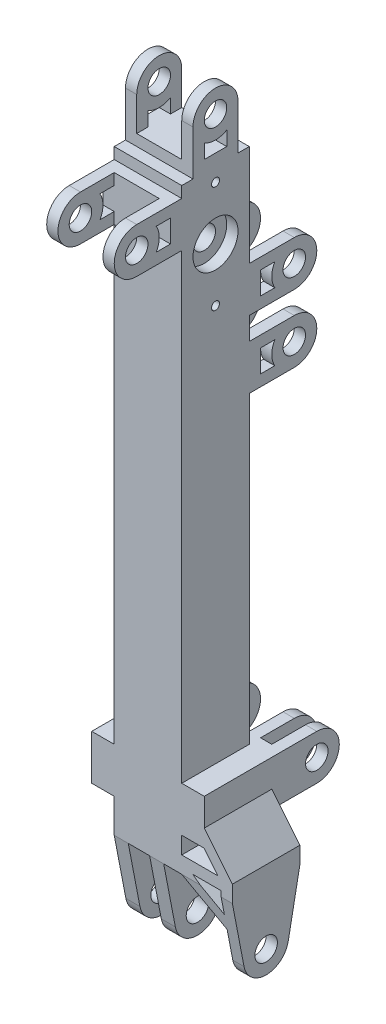
SolidWorks part; units mm, degrees
ref_plane "Front Plane" through (0, 0, 0) normal (0, 0, 1) x (1, 0, 0)
ref_plane "Top Plane" through (0, 0, 0) normal (0, 1, 0) x (1, 0, 0)
ref_plane "Right Plane" through (0, 0, 0) normal (1, 0, 0) x (0, 0, -1)
sketch "Sketch1" plane through (0, 0, 0) normal (0, 1, 0) x (1, 0, 0)
  line L1 (-9.525, -9.525) -> (9.525, -9.525)
  line L2 (-9.525, -9.525) -> (-9.525, 9.525)
  line L3 (-9.525, 9.525) -> (9.525, 9.525)
  line L4 (9.525, -9.525) -> (9.525, 9.525)
  line L5 (-9.525, -9.525) -> (9.525, 9.525) construction
  line L6 (-9.525, 9.525) -> (9.525, -9.525) construction
  point P0 (0, 0)
  dimension "D1" = 19.05
extrude "Boss-Extrude1" add sketch "Sketch1" along normal blind 190.5
sketch "Sketch2" plane through (0, 0, 0) normal (0, 1, 0) x (1, 0, 0)
  line L1 (-6.35, -6.35) -> (6.35, -6.35)
  line L2 (-6.35, -6.35) -> (-6.35, 6.35)
  line L3 (-6.35, 6.35) -> (6.35, 6.35)
  line L4 (6.35, -6.35) -> (6.35, 6.35)
  line L5 (-6.35, -6.35) -> (6.35, 6.35) construction
  line L6 (-6.35, 6.35) -> (6.35, -6.35) construction
  point P0 (0, 0)
  dimension "D1" = 12.7
extrude "Cut-Extrude1" cut sketch "Sketch2" along normal blind 120.65 from offset 25.4 contours L3 L4 L1 L2
sketch "Sketch4" plane through (0, 0, 0) normal (1, 0, 0) x (0, 0, -1)
  line L0 (-9.525, 190.5) -> (9.525, 190.5) construction
  circle A0 centre (0, 171.45) radius 6.35
  dimension "D1" = 12.7
  dimension "D2" = 19.05
extrude "Cut-Extrude2" cut sketch "Sketch4" against normal blind 3.175 from surface contours A0 starting at face at (9.525, 95.25, 0)
extrude "Cut-Extrude3" cut sketch "Sketch4<3>" along normal blind 3.175 from surface starting at face at (-9.525, 95.25, 0)
sketch "Sketch4<3>" plane through (0, 0, 0) normal (1, 0, 0) x (0, 0, -1) same geometry as "Sketch4"
sketch "Sketch5" plane through (0, 0, 0) normal (1, 0, 0) x (0, 0, -1)
  circle A0 centre (0, 171.45) radius 3.175
  dimension "D1" = 6.35
extrude "Cut-Extrude4" cut sketch "Sketch5" against normal through all both and the other way through all contours A0
hole_wizard "#4-40 Tapped Hole1" positions "Sketch6" profile "Sketch7" tap size "#4-40" standard "ANSI Inch" end condition through all
sketch "Sketch6" plane through (9.525, 0, 0) normal (1, 0, 0) x (0, 0, -1)
  line L0 (0, 186.5312) -> (0, 156.3688) construction
  circle A0 centre (0, 171.45) radius 3.175 construction
  point P0 (0, 186.5312)
  point P2 (0, 156.3688)
  point P9 (0, 171.45)
  dimension "D1" = 30.1625
sketch "Sketch7" plane through (9.525, 186.5312, 0) normal (0, 1, 0) x (0, 0, -1)
  line L0 (0, 0) -> (0, 19.05)
  line L1 (0, 19.05) -> (1.1303, 19.05)
  line L2 (1.1303, 19.05) -> (1.1303, 0)
  line L5 (1.1303, 0) -> (0, 0)
  line L11 (0, -6.35) -> (0, 107.95) construction
  dimension "Thru Tap Drill Dia." = 2.2606
  dimension "Thru Tap Drill Depth" = 19.05
cosmetic thread "Hole Thread1" parameters "D2"=2.8448
cosmetic thread "Hole Thread2" parameters "D2"=2.8448
sketch "Sketch8" plane through (0, 0, 0) normal (1, 0, 0) x (0, 0, -1)
  line L0 (-9.525, 25.4) -> (9.525, 25.4) construction
  line L1 (-9.525, 190.5) -> (-9.525, 0) construction
  line L2 (9.525, 190.5) -> (9.525, 0) construction
  line L4 (9.525, 22.225) -> (6.2354, 5.1488)
  line L5 (-6.2354, 5.1488) -> (-9.525, 22.225)
  line L7 (-9.525, 0) -> (9.525, 0) construction
  line L8 (-9.525, 22.225) -> (-9.525, 0)
  line L9 (-9.525, 0) -> (0, 0)
  line L10 (0, 0) -> (9.525, 0)
  line L11 (9.525, 0) -> (9.525, 22.225)
  arc A0 (6.2354, 5.1488) -> (-6.2354, 5.1488) centre (0, 6.35) cw
  circle A1 centre (0, 6.35) radius 3.175
  dimension "D3" = 6.35
  dimension "D4" = 6.35
  dimension "D1" = 3.175
  dimension "D2" = 19.05
extrude "Cut-Extrude5" cut sketch "Sketch8" against normal through all both and the other way through all contours L9 A0 L5 L8 | L4 A0 L10 L11 | A1 region at (0, 6.7606, -7.7085) region at (0, 6.7606, 7.7085) region at (0, 6.35, 0)
sketch "Sketch9" plane through (0, 0, 0) normal (0, 0, 1) x (1, 0, 0)
  line L0 (-9.525, 22.225) -> (9.525, 22.225) construction
  line L12 (0, 0) -> (0, 42.162) construction
  line L13 (-5.5562, 22.225) -> (-5.5563, 0)
  line L14 (0.4673, 0) -> (-5.5563, 0)
  line L15 (0.4673, 22.225) -> (0.4673, 0)
  line L16 (0.4673, 22.225) -> (-5.5562, 22.225)
  line L17 (4.4361, 22.225) -> (4.4361, 0)
  line L18 (9.525, 0) -> (4.4361, 0)
  line L19 (9.525, 22.225) -> (9.525, 0)
  line L20 (9.525, 22.225) -> (4.4361, 22.225)
  line L21 (9.525, 5.1488) -> (9.525, 22.225) construction
  line L22 (-9.525, 0) -> (9.525, 0) construction
  line L24 (-9.525, 5.1488) -> (-9.525, 22.225) construction
  dimension "D2" = 3.9688
  dimension "D3" = 6.0236
  dimension "D4" = 3.9687
extrude "Cut-Extrude6" cut sketch "Sketch9" against normal through all both and the other way through all
hole_wizard "#4-40 Tapped Hole2" positions "Sketch10" profile "Sketch11" tap size "#4-40" standard "ANSI Inch" end condition up to next
sketch "Sketch10" plane through (-9.525, 0, 0) normal (-1, 0, 0) x (0, 0, 1)
  point P0 (0, 20.6375)
  point P2 (0, 14.2875)
  dimension "D1" = 1.5875
  dimension "D2" = 6.35
sketch "Sketch11" plane through (-9.525, 20.6375, 0) normal (0, 1, 0) x (0, 0, 1)
  line L0 (0, 0) -> (0, 3.9688)
  line L1 (0, 3.9688) -> (1.1303, 3.9688)
  line L2 (1.1303, 3.9688) -> (1.1303, 0)
  line L5 (1.1303, 0) -> (0, 0)
  line L11 (0, -6.35) -> (0, 107.95) construction
  dimension "Thru Tap Drill Dia." = 2.2606
  dimension "Thru Tap Drill Depth" = 3.9688
cosmetic thread "Hole Thread3" parameters "D2"=2.8448
cosmetic thread "Hole Thread4" parameters "D2"=2.8448
sketch "Sketch12" plane through (0, 0, 0) normal (1, 0, 0) x (0, 0, -1)
  line L0 (-9.525, 187.325) -> (-9.525, 174.625)
  line L1 (-9.525, 190.5) -> (-9.525, 22.225) construction
  line L2 (-9.525, 174.625) -> (-22.225, 174.625)
  line L3 (-9.525, 187.325) -> (-22.225, 187.325)
  line L4 (-12.7, 184.15) -> (-12.7, 177.8)
  line L5 (-12.7, 177.8) -> (-16.7257, 177.8)
  line L6 (-12.7, 184.15) -> (-16.7257, 184.15)
  line L7 (-14.7129, 184.15) -> (-14.7129, 187.325) construction
  line L8 (-14.7129, 177.8) -> (-14.7129, 174.625) construction
  line L9 (-12.7, 180.975) -> (-9.525, 180.975) construction
  line L10 (-9.525, 190.5) -> (9.525, 190.5) construction
  arc A0 (-22.225, 187.325) -> (-22.225, 174.625) centre (-22.225, 180.975) ccw
  circle A1 centre (-22.225, 180.975) radius 3.175
  arc A2 (-16.7257, 184.15) -> (-16.7257, 177.8) centre (-22.225, 180.975) cw
  dimension "D2" = 6.35
  dimension "D3" = 12.7
  dimension "D1" = 12.7
  dimension "D4" = 3.175
  dimension "D5" = 9.525
extrude "Boss-Extrude2" add sketch "Sketch12" along normal up to surface and the other way up to surface up to face at (9.525, 106.3625, 0) other way up to face at (-9.525, 71.7665, 0)
sketch "Sketch13" plane through (0, 187.325, 0) normal (0, 1, 0) x (1, 0, 0)
  line L0 (-9.525, -28.575) -> (9.525, -28.575) construction
  line L1 (-6.35, -12.7) -> (6.35, -12.7)
  line L2 (-6.35, -12.7) -> (-6.35, -28.575)
  line L3 (-6.35, -28.575) -> (6.35, -28.575)
  line L4 (6.35, -12.7) -> (6.35, -28.575)
  line L5 (0, -12.7) -> (0, 0) construction
  line L6 (9.525, -22.225) -> (9.525, -9.525) construction
  line L7 (9.525, -9.525) -> (-9.525, -9.525) construction
  dimension "D1" = 3.175
  dimension "D2" = 3.175
extrude "Cut-Extrude7" cut sketch "Sketch13" against normal up to next contours L2 L3 L4 L1
sketch "Sketch15" plane through (0, 0, 0) normal (1, 0, 0) x (0, 0, -1)
  line L11 (-6.35, 190.5) -> (6.35, 190.5)
  line L12 (-9.525, 190.5) -> (9.525, 190.5) construction
  line L13 (6.35, 190.5) -> (6.35, 203.2)
  line L14 (-6.35, 203.2) -> (-6.35, 190.5)
  line L15 (-3.175, 193.675) -> (3.175, 193.675)
  line L16 (3.175, 193.675) -> (3.175, 197.7007)
  line L17 (-3.175, 193.675) -> (-3.175, 197.7007)
  line L18 (0, 190.5) -> (0, 193.675) construction
  line L19 (3.175, 195.6879) -> (6.35, 195.6879) construction
  line L20 (-3.175, 195.6879) -> (-6.35, 195.6879) construction
  arc A3 (6.35, 203.2) -> (-6.35, 203.2) centre (0, 203.2) ccw
  circle A4 centre (0, 203.2) radius 3.175
  arc A5 (-3.175, 197.7007) -> (3.175, 197.7007) centre (0, 203.2) ccw
  dimension "D8" = 6.35
  dimension "D5" = 12.7
  dimension "D6" = 12.7
  dimension "D7" = 3.175
extrude "Boss-Extrude3" add sketch "Sketch15" along normal up to surface and the other way up to surface up to face at (9.525, 143.6687, 8.7313) other way up to face at (-9.525, 115.4499, 6.985)
sketch "Sketch16" plane through (0, 0, -6.35) normal (0, 0, -1) x (-1, 0, 0)
  line L0 (9.525, 209.55) -> (-9.525, 209.55) construction
  line L1 (-6.35, 209.55) -> (6.35, 209.55)
  line L2 (-6.35, 209.55) -> (-6.35, 193.675)
  line L3 (-6.35, 193.675) -> (6.35, 193.675)
  line L4 (6.35, 209.55) -> (6.35, 193.675)
  line L5 (-9.525, 190.5) -> (9.525, 190.5) construction
  line L7 (0, 193.675) -> (0, 190.5) construction
  line L8 (-9.525, 190.5) -> (9.525, 190.5) construction
  line L9 (6.35, 201.6125) -> (9.525, 201.6125) construction
  line L10 (9.525, 203.2) -> (9.525, 190.5) construction
  line L11 (-6.35, 201.6125) -> (-9.525, 201.6125) construction
  line L12 (-9.525, 203.2) -> (-9.525, 190.5) construction
  dimension "D1" = 3.175
extrude "Cut-Extrude8" cut sketch "Sketch16" against normal up to next
sketch "Sketch17" plane through (0, 0, 0) normal (1, 0, 0) x (0, 0, -1)
  line L1 (9.525, 161.925) -> (9.525, 149.225)
  line L7 (9.525, 190.5) -> (9.525, 22.225) construction
  line L8 (9.525, 149.225) -> (22.225, 149.225)
  line L9 (22.225, 161.925) -> (9.525, 161.925)
  line L10 (12.7, 158.75) -> (12.7, 152.4)
  line L12 (12.7, 152.4) -> (16.7257, 152.4)
  line L21 (12.7, 158.75) -> (16.7257, 158.75)
  line L22 (14.7129, 152.4) -> (14.7129, 149.225) construction
  line L23 (12.7, 155.575) -> (9.525, 155.575) construction
  line L24 (14.7129, 158.75) -> (14.7129, 161.925) construction
  line L25 (6.35, 190.5) -> (9.525, 190.5) construction
  arc A6 (22.225, 149.225) -> (22.225, 161.925) centre (22.225, 155.575) ccw
  circle A7 centre (22.225, 155.575) radius 3.175
  arc A8 (16.7257, 152.4) -> (16.7257, 158.75) centre (22.225, 155.575) cw
  dimension "D2" = 6.35
  dimension "D3" = 12.7
  dimension "D1" = 12.7
  dimension "D4" = 3.175
  dimension "D9" = 34.925
extrude "Boss-Extrude4" add sketch "Sketch17" along normal up to surface and the other way up to surface up to face at (9.525, 161.925, 5.8208) other way up to face at (-9.525, 139.1606, 4.9893)
sketch "Sketch18" plane through (0, 161.925, 0) normal (0, 1, 0) x (1, 0, 0)
  line L0 (9.525, 28.575) -> (-9.525, 28.575) construction
  line L1 (-6.35, 28.575) -> (6.35, 28.575)
  line L2 (-6.35, 28.575) -> (-6.35, 12.7)
  line L3 (-6.35, 12.7) -> (6.35, 12.7)
  line L4 (6.35, 28.575) -> (6.35, 12.7)
  line L5 (0, 12.7) -> (0, 9.525) construction
  line L6 (9.525, 9.525) -> (-9.525, 9.525) construction
  line L7 (6.35, 20.6375) -> (9.525, 20.6375) construction
  line L8 (9.525, 9.525) -> (9.525, 22.225) construction
  line L9 (-6.35, 20.6375) -> (-9.525, 20.6375) construction
  dimension "D1" = 3.175
extrude "Cut-Extrude9" cut sketch "Sketch18" against normal up to next
sketch "Sketch19" plane through (0, 0, 0) normal (1, 0, 0) x (0, 0, -1)
  line L1 (9.525, 142.875) -> (9.525, 130.175)
  line L8 (9.525, 130.175) -> (22.225, 130.175)
  line L9 (22.225, 142.875) -> (9.525, 142.875)
  line L10 (12.7, 139.7) -> (12.7, 133.35)
  line L12 (12.7, 133.35) -> (16.7257, 133.35)
  line L18 (9.525, 149.225) -> (9.525, 22.225) construction
  line L19 (6.35, 190.5) -> (9.525, 190.5) construction
  line L21 (12.7, 139.7) -> (16.7257, 139.7)
  line L22 (14.7129, 133.35) -> (14.7129, 130.175) construction
  line L23 (12.7, 136.525) -> (9.525, 136.525) construction
  line L24 (14.7129, 139.7) -> (14.7129, 142.875) construction
  arc A6 (22.225, 130.175) -> (22.225, 142.875) centre (22.225, 136.525) ccw
  circle A7 centre (22.225, 136.525) radius 3.175
  arc A8 (16.7257, 133.35) -> (16.7257, 139.7) centre (22.225, 136.525) cw
  dimension "D2" = 6.35
  dimension "D3" = 12.7
  dimension "D1" = 12.7
  dimension "D4" = 3.175
  dimension "D5" = 47.625
extrude "Boss-Extrude5" add sketch "Sketch19" along normal up to surface and the other way up to surface up to face at (9.525, 160.3375, 0) other way up to face at (-9.525, 142.8083, 0)
sketch "Sketch20" plane through (0, 142.875, 0) normal (0, 1, 0) x (1, 0, 0)
  line L1 (-6.35, 12.7) -> (6.35, 12.7)
  line L2 (-6.35, 12.7) -> (-6.35, 28.575)
  line L3 (-6.35, 28.575) -> (6.35, 28.575)
  line L4 (6.35, 12.7) -> (6.35, 28.575)
extrude "Cut-Extrude10" cut sketch "Sketch20" against normal up to next
ref_plane "Plane1" through (0, 38.1, 0) normal (0, -1, 0) x (-1, 0, 0)
sketch "Sketch24" plane through (0, 38.1, 0) normal (0, -1, 0) x (-1, 0, 0)
  line L0 (15.875, -9.525) -> (15.875, 28.575)
  line L1 (15.875, 28.575) -> (12.7, 28.575)
  line L2 (12.7, 28.575) -> (12.7, 12.7)
  line L3 (12.7, 12.7) -> (9.525, 12.7)
  line L4 (9.525, 12.7) -> (9.525, 28.575)
  line L5 (9.525, 28.575) -> (6.35, 28.575)
  line L6 (6.35, 28.575) -> (6.35, 12.7)
  line L7 (6.35, 12.7) -> (-6.35, 12.7)
  line L8 (-6.35, 12.7) -> (-6.35, 28.575)
  line L9 (-6.35, 28.575) -> (-9.525, 28.575)
  line L10 (-9.525, 28.575) -> (-9.525, 12.7)
  line L11 (-9.525, 12.7) -> (-12.7, 12.7)
  line L12 (-12.7, 12.7) -> (-12.7, 28.575)
  line L13 (-12.7, 28.575) -> (-15.875, 28.575)
  line L14 (-15.875, 28.575) -> (-15.875, -9.525)
  line L15 (-15.875, -9.525) -> (-9.525, -9.525)
  line L16 (-9.525, -9.525) -> (-9.525, 9.525)
  line L17 (-9.525, 9.525) -> (9.525, 9.525)
  line L18 (9.525, 9.525) -> (9.525, -9.525)
  line L19 (9.525, -9.525) -> (15.875, -9.525)
  line L20 (0, 12.7) -> (0, 9.525) construction
  line L21 (-9.525, 9.525) -> (9.525, 9.525) construction
  line L22 (9.525, 9.525) -> (9.525, 6.35) construction
  line L23 (-9.525, -9.525) -> (-4.4361, -9.525) construction
  dimension "D1" = 12.7
  dimension "D2" = 3.175
  dimension "D4" = 19.05
extrude "Boss-Extrude6" add sketch "Sketch24" along normal mid plane 12.7 contours L14 L15 L16 L17 L18 L19 L0 L1 L2 L3 L4 L5 L6 L7 L8 L9 L10 L11 L12 L13
sketch "Sketch25" plane through (0, 0, 0) normal (1, 0, 0) x (0, 0, -1)
  line L0 (-39.3712, 38.1) -> (39.3712, 38.1) construction
  line L1 (28.575, 31.75) -> (28.575, 44.45) construction
  line L2 (28.575, 44.45) -> (-9.525, 44.45) construction
  line L3 (22.225, 44.45) -> (28.575, 44.45)
  line L4 (28.575, 44.45) -> (28.575, 38.1)
  line L5 (28.575, 38.1) -> (28.575, 31.75)
  line L6 (28.575, 31.75) -> (22.225, 31.75)
  arc A0 (22.225, 31.75) -> (22.225, 44.45) centre (22.225, 38.1) ccw
  circle A1 centre (22.225, 38.1) radius 3.175
  dimension "D1" = 6.35
extrude "Cut-Extrude11" cut sketch "Sketch25" against normal through all both and the other way through all contours A0 L4 L3 | A0 L6 L5 | A1 region at (0, 33.1684, -27.1566) region at (0, 43.0316, -27.1566)
sketch "Sketch23" plane through (0, 0, 0) normal (0, 0, 1) x (1, 0, 0)
  line L0 (12.7, 23.7656) -> (20.6375, 23.7656)
  line L1 (20.6375, 23.7656) -> (20.6375, 17.5122)
  line L2 (20.6375, 0) -> (23.8125, 0)
  line L3 (23.8125, 0) -> (23.8125, 26.9406)
  line L4 (19.7146, 26.9406) -> (9.525, 26.9406)
  line L5 (9.525, 174.625) -> (9.525, 44.45) construction
  line L6 (20.6375, 13.4703) -> (20.6375, 0)
  line L8 (9.525, 22.225) -> (9.525, 26.9406)
  line L9 (16.6687, 23.7656) -> (16.6687, 26.9406) construction
  line L10 (22.225, 0) -> (22.225, 12.7) construction
  line L11 (20.6375, 13.4703) -> (9.525, 22.225)
  line L12 (20.6375, 13.4703) -> (23.8125, 13.4703) construction
  line L13 (20.6375, 17.5122) -> (12.7, 23.7656)
  line L14 (16.6687, 20.6389) -> (14.7039, 18.1449) construction
  line L16 (19.7146, 26.9406) -> (15.7902, 31.75)
  line L17 (23.8125, 26.9406) -> (15.875, 36.668)
  line L21 (15.875, 31.75) -> (9.525, 31.75) construction
  line L22 (17.7524, 29.3453) -> (20.2124, 31.3526) construction
  line L23 (15.875, 36.668) -> (9.525, 44.45) construction
  line L24 (15.875, 31.75) -> (15.875, 44.45) construction
  line L25 (15.7902, 31.75) -> (15.875, 31.75)
  line L26 (15.875, 31.75) -> (15.875, 36.668)
  dimension "D1" = 14.2875
  dimension "D2" = 3.175
  dimension "D3" = 12.7
  dimension "D4" = 3.175
extrude "Boss-Extrude7" add sketch "Sketch23" along normal up to surface and the other way up to surface up to face at (-0.0435, 51.0117, 9.525) other way up to face at (-0.0933, 24.9464, -9.525)
sketch "Sketch28" plane through (23.8125, 0, 0) normal (1, 0, 0) x (0, 0, -1)
  line L0 (9.525, 22.225) -> (6.2354, 5.1488) construction
  line L1 (9.525, 13.4703) -> (9.525, 22.225) construction
  line L2 (9.525, 0) -> (9.525, 13.4703) construction
  line L3 (-9.525, 0) -> (9.525, 0) construction
  line L4 (-6.2354, 5.1488) -> (-9.525, 22.225) construction
  line L5 (-9.525, 13.4703) -> (-9.525, 22.225) construction
  line L6 (-9.525, 0) -> (-9.525, 13.4703) construction
  line L7 (9.525, 22.225) -> (6.2354, 5.1488)
  line L8 (9.525, 13.4703) -> (9.525, 22.225)
  line L9 (9.525, 0) -> (9.525, 13.4703)
  line L10 (-9.525, 0) -> (9.525, 0)
  line L11 (-6.2354, 5.1488) -> (-9.525, 22.225)
  line L12 (-9.525, 13.4703) -> (-9.525, 22.225)
  line L13 (-9.525, 0) -> (-9.525, 13.4703)
  arc A0 (-6.2354, 5.1488) -> (6.2354, 5.1488) centre (0, 6.35) ccw construction
  arc A1 (-6.2354, 5.1488) -> (6.2354, 5.1488) centre (0, 6.35) ccw
  circle A2 centre (0, 6.35) radius 3.175
  line M2 (-9.525, 26.9406) -> (-9.525, 0)
  line M3 (-9.525, 0) -> (9.525, 0)
  line M4 (9.525, 0) -> (9.525, 26.9406)
  dimension "D1" = 6.35
extrude "Cut-Extrude13" cut sketch "Sketch28" against normal up to next contours A1 L10 L7 M4 | A1 L11 M2 M3 | A2 region at (23.8125, 6.7606, -7.7085) region at (23.8125, 6.7606, 7.7085)
